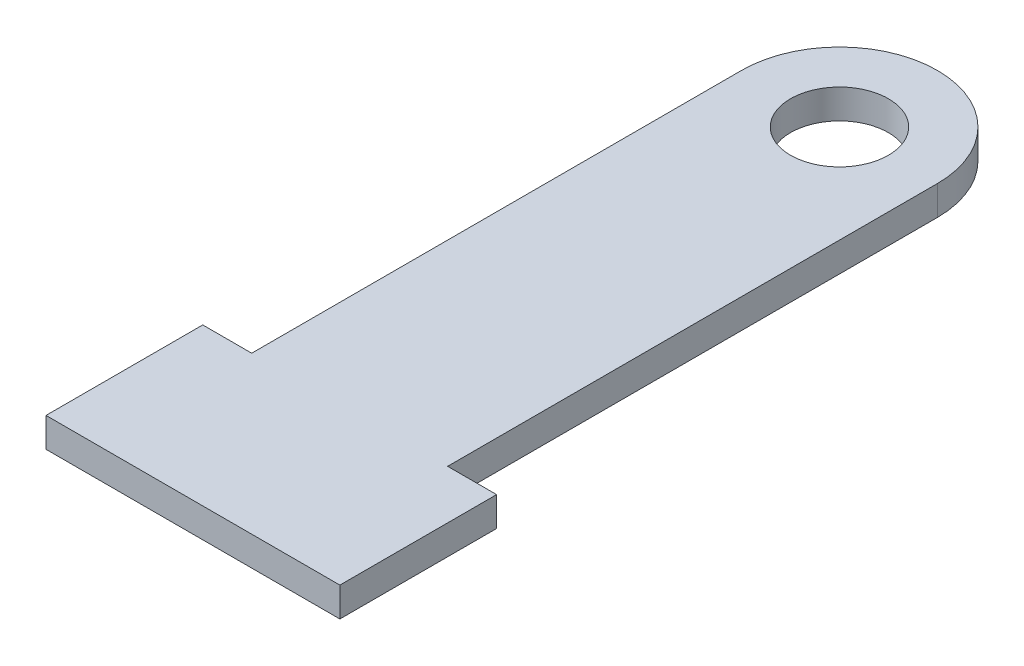
SolidWorks part; units mm, degrees
note: '?' marks a value the reader was unsure of.
material "Copper-Cobalt-Beryllium alloy, UNS C17500"
ref_plane "Front Plane" through (0, 0, 0) normal (0, 0, 1) x (1, 0, 0)
ref_plane "Top Plane" through (0, 0, 0) normal (0, 1, 0) x (1, 0, 0)
ref_plane "Right Plane" through (0, 0, 0) normal (1, 0, 0) x (0, 0, -1)
ref_axis "Axis X" through (34.7212, 0, 0) along (-1, 0, 0)?
ref_axis "Axis Y" through (0, 66.2093, 0) along (0, -1, 0)?
ref_axis "Axis Z" through (0, 0, -66.3201) along (0, 0, 1)?
sketch "Sketch1" plane through (0, 0, 0) normal (0, 1, 0) x (1, 0, 0)
  line L0 (-58.7593, 0) -> (58.7593, 0) construction
  line L2 (-1, 0) -> (-1, 5)
  line L4 (1, 0) -> (1, 5)
  line L5 (0, 0.6356) -> (0, 4.3589) construction
  line L6 (-1.5, 0) -> (-1, 0)
  line L7 (-1.5, 0) -> (-1.5, -1.6)
  line L8 (-1.5, -1.6) -> (1.5, -1.6)
  line L9 (1.5, 0) -> (1.5, -1.6)
  line L10 (0, -68.6131) -> (0, 68.6131) construction
  line L11 (1, 0) -> (1.5, 0)
  arc A0 (1, 5) -> (-1, 5) centre (0, 5) ccw
  circle A1 centre (0, 5) radius 0.5
  dimension "D5" = 5
  dimension "D2" = 1
  dimension "D1" = 2
  dimension "D3" = 3
  dimension "D4" = 1.6
base flange "Base-Flange1" sketch "Sketch1" thickness 0.3 reverse thickness direction no parameters "D1"=1.5
sketch "Bend-Lines1" [suppressed] plane through (0, 0, 0) normal (0, 1, 0) x (1, 0, 0)
sketch "Bounding-Box1" [suppressed] plane through (0, 0, 0) normal (0, 1, 0) x (1, 0, 0)
sheet metal parameters "Sheet-Metal18" thickness 0.3 parameters "D1"=1.5
flat pattern "Flat-Pattern18" [suppressed]
sketch "Bend-Lines2" plane through (0, 0, 0) normal (0, 1, 0) x (1, 0, 0)
sketch3d "Bounding-Box2" [suppressed]
  line L0 (-2, 0.9996, 0) -> (-2, -6.6, 0) construction
  line L1 (2, 0.9996, 0) -> (2, -6.6, 0) construction
  line L2 (-2, 0.9996, 0) -> (2, 0.9996, 0) construction
  line L3 (-2, -6.6, 0) -> (2, -6.6, 0) construction
